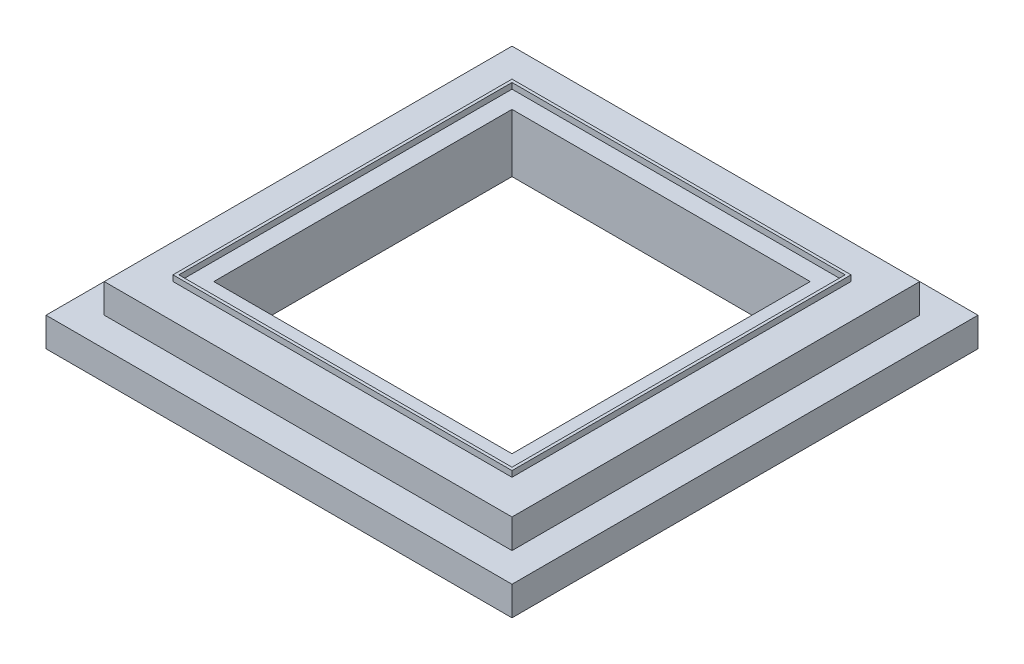
SolidWorks part; units mm, degrees
note: The reader was unsure of these and kept them because the rebuilt part matched: shared geometry of "Эскиз2<3>".
ref_plane "Спереди" through (0, 0, 0) normal (0, 0, 1) x (1, 0, 0)
ref_plane "Сверху" through (0, 0, 0) normal (0, 1, 0) x (1, 0, 0)
ref_plane "Справа" through (0, 0, 0) normal (1, 0, 0) x (0, 0, -1)
sketch "Эскиз1" plane through (0, 0, 0) normal (0, 1, 0) x (1, 0, 0)
  line L1 (-40, -40) -> (40, -40)
  line L2 (-40, -40) -> (-40, 40)
  line L3 (-40, 40) -> (40, 40)
  line L4 (40, -40) -> (40, 40)
  line L5 (-40, -40) -> (40, 40) construction
  line L6 (-40, 40) -> (40, -40) construction
  point P1 (0, 0)
  dimension "D1" = 80
ref_plane "Плоскость4" through (0, 5, 0) normal (0, 1, 0) x (1, 0, 0)
sketch "Эскиз2" plane through (0, 5, 0) normal (0, 1, 0) x (1, 0, 0)
  line L1 (-35, -35) -> (35, -35)
  line L2 (-35, -35) -> (-35, 35)
  line L3 (-35, 35) -> (35, 35)
  line L4 (-40, -40) -> (40, -40)
  line L5 (40, -40) -> (40, 40)
  line L6 (40, 40) -> (-40, 40)
  line L7 (-40, 40) -> (-40, -40)
  line L8 (-40, -40) -> (40, -40)
  line L9 (40, -40) -> (40, 40)
  line L10 (40, 40) -> (-40, 40)
  line L11 (-40, 40) -> (-40, -40)
  line L12 (35, -35) -> (35, 35)
  line L13 (-35, -35) -> (35, 35) construction
  line L14 (-35, 35) -> (35, -35) construction
  point P2 (0, 0)
  dimension "D2" = 70
  dimension "D1" = 0
ref_plane "Плоскость5" through (0, 10, 0) normal (0, 1, 0) x (1, 0, 0)
sketch "Эскиз3" plane through (0, 10, 0) normal (0, 1, 0) x (1, 0, 0)
  line L0 (-35, -35) -> (35, -35) construction
  line L1 (-35, -35) -> (-35, 35) construction
  line L2 (-35, 35) -> (35, 35) construction
  line L3 (35, -35) -> (35, 35) construction
  line L4 (-35, -35) -> (35, -35)
  line L5 (-35, -35) -> (-35, 35)
  line L6 (-35, 35) -> (35, 35)
  line L7 (35, -35) -> (35, 35)
loft "По сечениям1" add profiles "Эскиз1" section "Эскиз1" section "Эскиз2" start constraint default
loft "По сечениям2" add profiles "Эскиз3" section "Эскиз2<3>" section "Эскиз3"
sketch "Эскиз2<3>" plane through (0, 5, 0) normal (0, 1, 0) x (1, 0, 0) same geometry as "Эскиз2"
sketch "Эскиз4" plane through (0, 10, 0) normal (0, 1, 0) x (1, 0, 0)
  line L1 (-25.6, -25.6) -> (25.6, -25.6)
  line L2 (-25.6, -25.6) -> (-25.6, 25.6)
  line L3 (-25.6, 25.6) -> (25.6, 25.6)
  line L4 (25.6, -25.6) -> (25.6, 25.6)
  line L5 (-25.6, -25.6) -> (25.6, 25.6) construction
  line L6 (-25.6, 25.6) -> (25.6, -25.6) construction
  point P0 (0, 0)
  dimension "D1" = 51.2
extrude "Вырез-Вытянуть1" cut sketch "Эскиз4" against normal through all
sketch "Эскиз5" plane through (0, 10, 0) normal (0, 1, 0) x (1, 0, 0)
  line L4 (-35, 35) -> (-35, -35)
  line L5 (-35, -35) -> (35, -35)
  line L6 (35, -35) -> (35, 35)
  line L7 (35, 35) -> (-35, 35)
  line L8 (-35, 35) -> (-35, -35)
  line L9 (-35, -35) -> (35, -35)
  line L10 (35, -35) -> (35, 35)
  line L11 (35, 35) -> (-35, 35)
  line L18 (-29.1, 29.1) -> (-29.1, -29.1)
  line L19 (-29.1, -29.1) -> (29.1, -29.1)
  line L20 (29.1, -29.1) -> (29.1, 29.1)
  line L21 (29.1, 29.1) -> (-29.1, 29.1)
  line L22 (-28.6, -28.6) -> (28.6, -28.6)
  line L23 (28.6, -28.6) -> (28.6, 28.6)
  line L24 (28.6, 28.6) -> (-28.6, 28.6)
  line L25 (-28.6, 28.6) -> (-28.6, -28.6)
  line L26 (-28.6, -28.6) -> (28.6, -28.6)
  line L27 (28.6, -28.6) -> (28.6, 28.6)
  line L28 (28.6, 28.6) -> (-28.6, 28.6)
  line L29 (-28.6, 28.6) -> (-28.6, -28.6)
  dimension "D1" = 0
  dimension "D2" = 3
  dimension "D3" = 0.5
extrude "Бобышка-Вытянуть1" add sketch "Эскиз5" along normal blind 1 contours L20 L21 L18 L19 L29 L28 L27 L26
